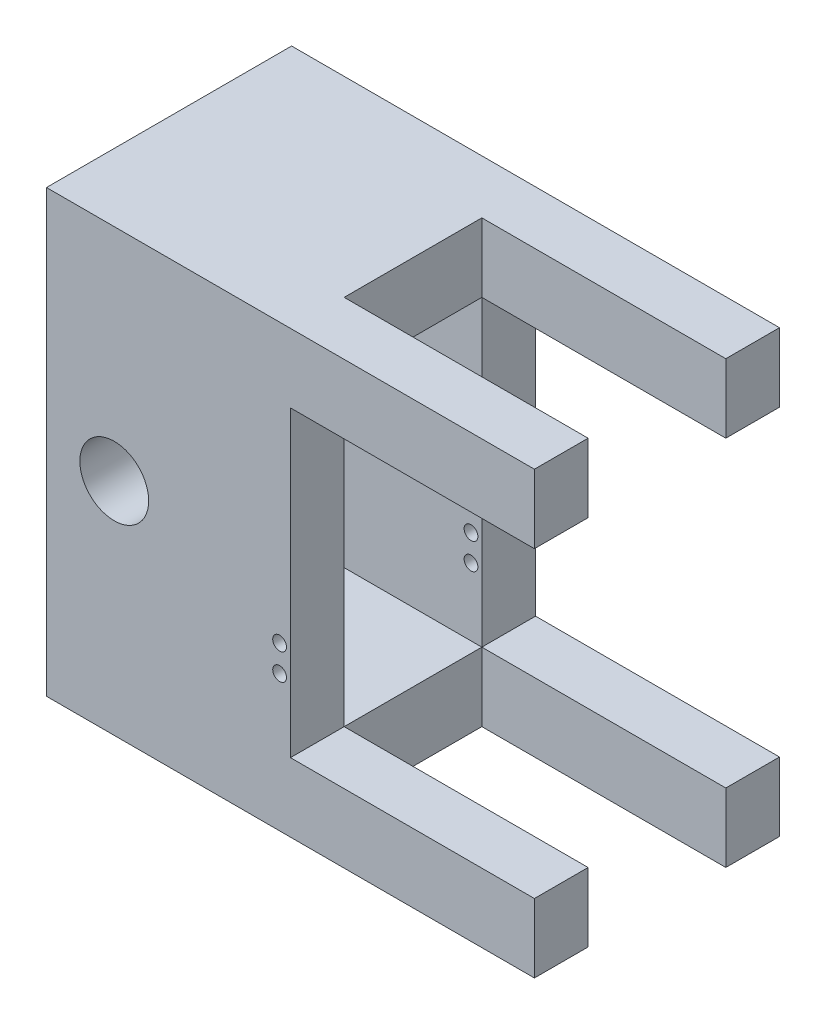
SolidWorks part; units mm, degrees
ref_plane "Front Plane" through (0, 0, 0) normal (1, 0, 0) x (0, 1, 0)
ref_plane "Top Plane" through (0, 0, 0) normal (0, 0, 1) x (0, 1, 0)
ref_plane "Right Plane" through (0, 0, 0) normal (0, 1, 0) x (-1, 0, 0)
sketch "Sketch1" plane through (0, 0, 0) normal (1, 0, 0) x (0, 1, 0)
  line L0 (12.7, 45.212) -> (12.7, 0)
  line L1 (0, 0) -> (81.28, 0)
  line L2 (0, 0) -> (0, 45.212)
  line L3 (0, 45.212) -> (81.28, 45.212)
  line L4 (81.28, 0) -> (81.28, 45.212)
  line L5 (68.58, 45.212) -> (68.58, 0)
  line L6 (12.7, 35.306) -> (0, 35.306)
  line L7 (0, 9.906) -> (12.7, 9.906)
  line L8 (81.28, 9.906) -> (68.58, 9.906)
  line L9 (68.58, 35.306) -> (81.28, 35.306)
  line L10 (12.7, 35.306) -> (68.58, 35.306)
  line L11 (12.7, 9.906) -> (68.58, 9.906)
  dimension "D1" = 81.28
  dimension "D2" = 45.212
  dimension "D3" = 12.7
  dimension "D4" = 12.7
  dimension "D5" = 25.4
  dimension "D6" = 9.906
extrude "Boss-Extrude1" add sketch "Sketch1" along normal blind 90 contours L4 L8 L5 L1 | L6 L0 L3 L2 | L7 L2 L1 L0 | L5 L9 L4 L3 region at (0, 6.35, 40.259) region at (0, 74.93, 40.259) region at (0, 6.35, 4.953) region at (0, 74.93, 4.953)
extrude "Boss-Extrude2" add sketch "Sketch1<4>" along normal blind 45 contours L0 L10 L5 L3 | L2 L7 L0 L6 | L9 L5 L8 L4 | L11 L0 L1 L5 region at (0, 40.64, 40.259) region at (0, 6.35, 22.606) region at (0, 40.64, 4.953) region at (0, 74.93, 22.606)
sketch "Sketch1<4>" plane through (0, 0, 0) normal (1, 0, 0) x (0, 1, 0) same geometry as "Sketch1"
extrude "Boss-Extrude3" add sketch "Sketch1<5>" along normal blind 5 contours L0 L11 L5 L10 region at (0, 40.64, 22.606)
sketch "Sketch1<5>" plane through (0, 0, 0) normal (1, 0, 0) x (0, 1, 0) same geometry as "Sketch1"
sketch "Sketch3" plane through (0, 0, 45.212) normal (0, 0, 1) x (1, 0, 0)
  line L0 (45, 30) -> (0, 30)
  line L1 (43, 30) -> (43, 25.1359)
  line L3 (45, 12.7) -> (45, 68.58) construction
  line L4 (0, 0) -> (0, 81.28) construction
  line L5 (43, 30) -> (43, 0)
  line L6 (90, 0) -> (0, 0) construction
  line L8 (45, 40.64) -> (0, 40.64)
  circle A0 centre (43, 30) radius 1.27
  circle A1 centre (12.5, 40.64) radius 6.35
  circle A2 centre (43, 25.1359) radius 1.27
  dimension "D1" = 2.54
  dimension "D4" = 12.7
  dimension "D2" = 30
  dimension "D3" = 2
  dimension "D5" = 12.5
  dimension "D6" = 4.8641
extrude "Cut-Extrude1" cut sketch "Sketch3" against normal through all contours L5 A0 L0 | L0 A0 | L0 A0 L5 | L8 A1 | L8 A1 | L1 A2 L5 | L5 A2 L1 region at (43.539, 29.461, 45.212) region at (43, 30.539, 45.212) region at (43.539, 25.1359, 45.212) region at (42.461, 25.1359, 45.212) region at (42.461, 29.461, 45.212) region at (12.5, 37.945, 45.212) region at (12.5, 43.335, 45.212)
